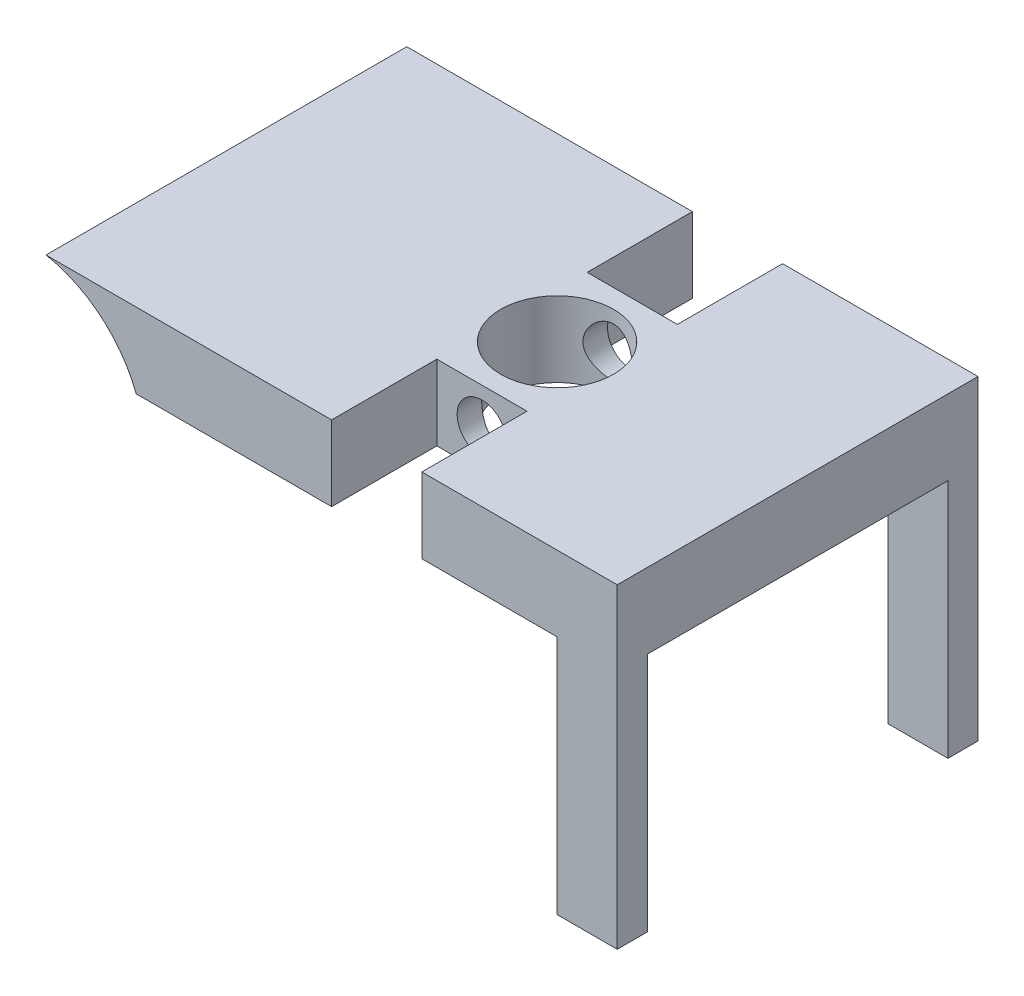
SolidWorks part; units mm, degrees
ref_plane "Front Plane" through (0, 0, 0) normal (0, 0, 1) x (1, 0, 0)
ref_plane "Top Plane" through (0, 0, 0) normal (0, 1, 0) x (1, 0, 0)
ref_plane "Right Plane" through (0, 0, 0) normal (1, 0, 0) x (0, 0, -1)
sketch "Sketch3" plane through (0, 0, 0) normal (0, 0, 1) x (1, 0, 0)
  line L1 (-13, -2.5) -> (19, -2.5)
  line L3 (-19, 2.5) -> (19, 2.5)
  line L4 (19, -2.5) -> (19, 2.5)
  line L5 (-13.3306, -1.754) -> (19, 2.5) construction
  line L6 (-19, 2.5) -> (19, -2.5) construction
  line L9 (-19, 2.5) -> (-12.2782, 2.5) construction
  arc A1 (-19, 2.5) -> (-13, -2.5) centre (-20.4698, -5.3638) cw
  point P0 (0, 0)
  point P2 (-13.5901, -1.8224)
  point P6 (0, 2.5)
  point P11 (-19, 2.2504)
  dimension "D5" = 6
  dimension "D2" = 8
  dimension "D1" = 38
  dimension "D4" = 5
extrude "Boss-Extrude1" add sketch "Sketch3" along normal mid plane 24
sketch "Sketch4" plane through (0, 0, 12) normal (0, 0, 1) x (1, 0, 0)
  line L0 (19, -2.5) -> (19, 2.5) construction
  line L1 (19, 2.5) -> (-19, 2.5) construction
  line L2 (6, -2.5) -> (0, -2.5)
  line L3 (6, -2.5) -> (6, 2.5)
  line L4 (6, 2.5) -> (0, 2.5)
  line L5 (0, -2.5) -> (0, 2.5)
  line L6 (6, -2.5) -> (0, 2.5) construction
  line L7 (6, 2.5) -> (0, -2.5) construction
  circle A2 centre (3, 0) radius 1.65
  dimension "D1" = 3.3
  dimension "D2" = 5
  dimension "D5" = 16
extrude "Cut-Extrude1" cut sketch "Sketch4" against normal up to next contours A2 region at (3, 0, 12)
extrude "Cut-Extrude3" cut sketch "Sketch4<3>" against normal blind 7
sketch "Sketch4<3>" plane through (0, 0, 12) normal (0, 0, 1) x (1, 0, 0) same geometry as "Sketch4"
mirror "Mirror1" about plane through (0, 0, 0) normal (0, 0, 1) of "Cut-Extrude3"
sketch "Sketch5" plane through (0, 2.5, 0) normal (0, 1, 0) x (1, 0, 0)
  line L0 (19, -12) -> (19, 12) construction
  circle A0 centre (3, 0) radius 3.75
  point P7 (19, 0)
  dimension "D2" = 7.5
  dimension "D1" = 16
extrude "Cut-Extrude2" cut sketch "Sketch5" against normal up to next
sketch "Sketch6" plane through (0, 0, 12) normal (0, 0, 1) x (1, 0, 0)
  line L0 (19, -2.5) -> (19, -18.5)
  line L1 (19, -18.5) -> (15, -18.5)
  line L2 (15, -18.5) -> (15, -2.5)
  line L3 (6, -2.5) -> (19, -2.5) construction
  line L4 (15, -2.5) -> (19, -2.5)
  dimension "D1" = 16
  dimension "D2" = 4
extrude "Boss-Extrude2" add sketch "Sketch6" against normal up to surface (24 mm away) up to face at (12.5, 0, -12)
sketch "Sketch7" plane through (15, 0, 0) normal (-1, 0, 0) x (0, 0, 1)
  line L0 (-12, -18.5) -> (12, -18.5) construction
  line L1 (-10, -18.5) -> (10, -18.5)
  line L2 (-10, -18.5) -> (-10, -2.5)
  line L3 (-10, -2.5) -> (10, -2.5)
  line L4 (10, -18.5) -> (10, -2.5)
  line L5 (-12, -2.5) -> (12, -2.5) construction
  line L6 (-12, -2.5) -> (-12, -18.5) construction
  point P8 (0, -2.5)
  dimension "D1" = 2
extrude "Cut-Extrude4" cut sketch "Sketch7" against normal up to next
